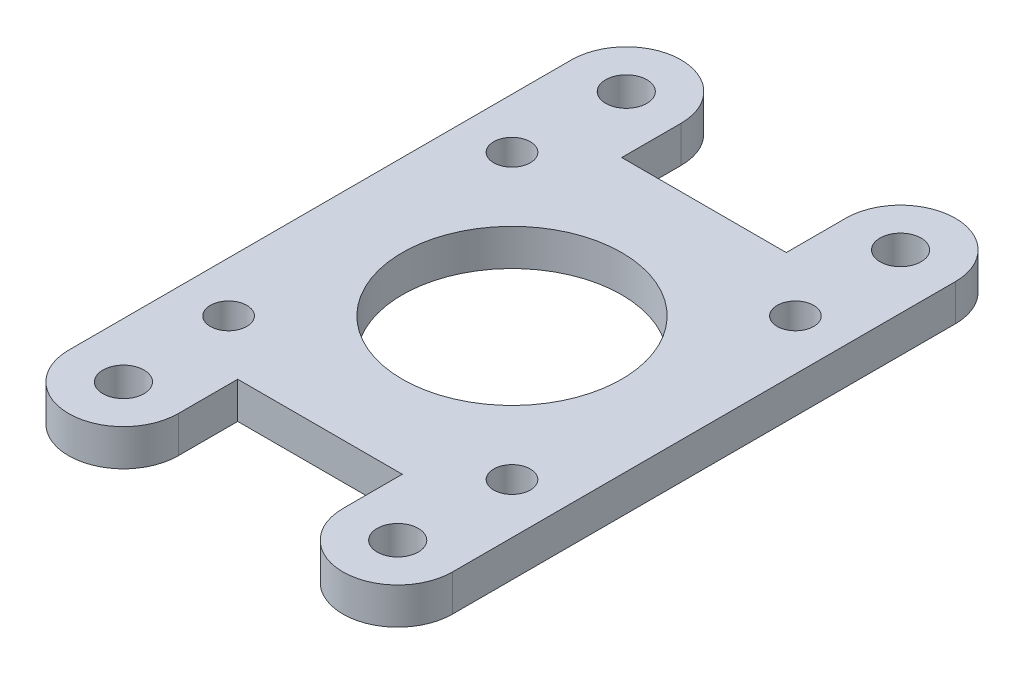
SolidWorks part; units mm, degrees
material "1060 Alloy"
ref_plane "Front Plane" through (0, 0, 0) normal (0, 0, 1) x (1, 0, 0)
ref_plane "Top Plane" through (0, 0, 0) normal (0, 1, 0) x (1, 0, 0)
ref_plane "Right Plane" through (0, 0, 0) normal (1, 0, 0) x (0, 0, -1)
sketch "Sketch1" plane through (0, 0, 0) normal (0, 1, 0) x (1, 0, 0)
  line L0 (21, -21) -> (-21, 21) construction
  line L1 (-21, 21) -> (21, 21)
  line L2 (-21, 21) -> (-21, -21)
  line L3 (-21, -21) -> (21, -21)
  line L4 (21, 21) -> (21, -21)
  dimension "D1" = 42
  dimension "D2" = 42
sheet metal parameters "Sheet-Metal1" thickness 4 parameters "D1"=5
base flange "Base-Flange1" sketch "Sketch1" thickness 4 reverse thickness direction no parameters "D1"=5
sketch "Sketch4" plane through (0, 0, 0) normal (0, 1, 0) x (1, 0, 0)
  line L0 (-15, 27.5) -> (-15, -27.5) construction
  line L1 (-9, 27.5) -> (-9, -27.5)
  line L2 (-21, 27.5) -> (-21, -27.5)
  line L3 (15, 27.5) -> (15, -27.5) construction
  line L4 (21, 27.5) -> (21, -27.5)
  line L5 (9, 27.5) -> (9, -27.5)
  line L6 (21, -21) -> (21, 21) construction
  line L7 (-21, 21) -> (-21, -21) construction
  line L8 (-15, 27.5) -> (15, -27.5) construction
  line L9 (-15, 0) -> (15, 0) construction
  arc A0 (-9, 27.5) -> (-21, 27.5) centre (-15, 27.5) ccw
  arc A1 (-21, -27.5) -> (-9, -27.5) centre (-15, -27.5) ccw
  arc A2 (21, 27.5) -> (9, 27.5) centre (15, 27.5) ccw
  arc A3 (9, -27.5) -> (21, -27.5) centre (15, -27.5) ccw
  circle A4 centre (-15, 27.5) radius 2.25
  circle A5 centre (15, 27.5) radius 2.25
  circle A6 centre (15, -27.5) radius 2.25
  circle A7 centre (-15, -27.5) radius 2.25
  point P2 (-15, 0)
  point P7 (15, 0)
  dimension "D3" = 4.5
  dimension "D1" = 55
  dimension "D2" = 30
base flange "Tab1" sketch "Sketch4" thickness 4 reverse thickness direction no parameters "D1"=5
sketch "Sketch5" plane through (0, 0, 0) normal (0, 1, 0) x (1, 0, 0)
  line L0 (21, -21) -> (-21, 21) construction
  line L1 (-15.5, 15.5) -> (-15.5, -15.5) construction
  line L2 (-15.5, -15.5) -> (15.5, -15.5) construction
  line L3 (15.5, -15.5) -> (15.5, 15.5) construction
  line L4 (15.5, 15.5) -> (-15.5, 15.5) construction
  line L5 (-15.5, 15.5) -> (15.5, -15.5) construction
  circle A0 centre (0, 0) radius 12
  circle A1 centre (15.5, 15.5) radius 2
  circle A2 centre (15.5, -15.5) radius 2
  circle A3 centre (-15.5, -15.5) radius 2
  circle A4 centre (-15.5, 15.5) radius 2
  dimension "D2" = 4
  dimension "D3" = 24
  dimension "D1" = 31
extrude "Cut-Extrude1" cut sketch "Sketch5" against normal through all normal cut yes
flat pattern "Flat-Pattern1" [suppressed]
sketch "Bend-Lines1" plane through (0, 0, 0) normal (0, 1, 0) x (1, 0, 0)
sketch3d "Bounding-Box1" [suppressed]
  line L0 (21, 33.4999, 0) -> (21, -33.4999, 0) construction
  line L1 (-21, 33.4999, 0) -> (-21, -33.4999, 0) construction
  line L2 (21, 33.4999, 0) -> (-21, 33.4999, 0) construction
  line L3 (21, -33.4999, 0) -> (-21, -33.4999, 0) construction
